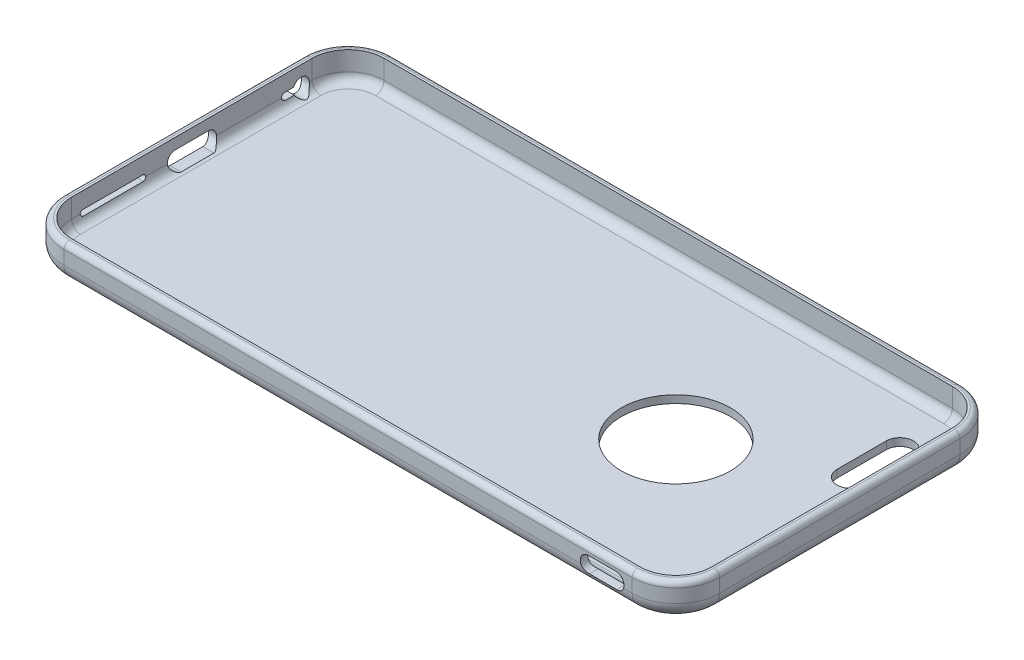
SolidWorks part; units mm, degrees
ref_plane "Front Plane" through (0, 0, 0) normal (0, 0, 1) x (1, 0, 0)
ref_plane "Top Plane" through (0, 0, 0) normal (0, 1, 0) x (1, 0, 0)
ref_plane "Right Plane" through (0, 0, 0) normal (1, 0, 0) x (0, 0, -1)
sketch "Sketch1" plane through (0, 0, 0) normal (0, 1, 0) x (1, 0, 0)
  line L1 (-76.2, -38.1) -> (76.2, -38.1)
  line L2 (-76.2, -38.1) -> (-76.2, 38.1)
  line L3 (-76.2, 38.1) -> (76.2, 38.1)
  line L4 (76.2, -38.1) -> (76.2, 38.1)
  dimension "D1" = 152.4
  dimension "D2" = 76.2
  dimension "D3" = 38.1
  dimension "D4" = 76.2
extrude "Boss-Extrude1" add sketch "Sketch1" along normal blind 8.255
fillet "Fillet1" radius 10.16 4 edges at (-76.2, 4.1275, -38.1) (76.2, 4.1275, -38.1) (76.2, 4.1275, 38.1) (-76.2, 4.1275, 38.1)
fillet "Fillet2" radius 3.81 8 edges at (73.2242, 0, -35.1242) (76.2, 0, 0) (73.2242, 0, 35.1242) (0, 0, 38.1) (-73.2242, 0, 35.1242) (-76.2, 0, 0) (-73.2242, 0, -35.1242) (0, 0, -38.1)
fillet "Fillet3" radius 1.27 8 edges at (73.2242, 8.255, -35.1242) (76.2, 8.255, 0) (73.2242, 8.255, 35.1242) (0, 8.255, 38.1) (-73.2242, 8.255, 35.1242) (-76.2, 8.255, 0) (-73.2242, 8.255, -35.1242) (0, 8.255, -38.1)
shell "Shell1" thickness 1.778 removed face at (0, 8.255, 0)
sketch "Sketch2" plane through (0, 0, 0) normal (0, -1, 0) x (1, 0, 0)
  circle A0 centre (38.1, 0) radius 12.7
  dimension "D1" = 25.4
  dimension "D2" = 38.1
extrude "Cut-Extrude1" cut sketch "Sketch2" against normal through all
sketch "Sketch3" plane through (0, 0, 0) normal (0, -1, 0) x (1, 0, 0)
  line L0 (66.04, -12.7) -> (66.04, -24.13) construction
  line L1 (69.215, -12.7) -> (69.215, -24.13)
  line L2 (62.865, -12.7) -> (62.865, -24.13)
  arc A0 (69.215, -12.7) -> (62.865, -12.7) centre (66.04, -12.7) ccw
  arc A1 (62.865, -24.13) -> (69.215, -24.13) centre (66.04, -24.13) ccw
  circle A2 centre (38.1, 0) radius 12.7 construction
  point P2 (66.04, -18.415)
  dimension "D1" = 12.7
  dimension "D2" = 11.43
  dimension "D3" = 3.175
  dimension "D4" = 27.94
extrude "Cut-Extrude2" cut sketch "Sketch3" against normal through all
sketch "Sketch4" plane through (0, 0, 0) normal (0, 0, 1) x (1, 0, 0)
  line L0 (62.23, 4.445) -> (55.88, 4.445) construction
  line L1 (62.23, 2.54) -> (55.88, 2.54)
  line L2 (62.23, 6.35) -> (55.88, 6.35)
  line L3 (74.93, 8.255) -> (66.04, 8.255) construction
  line L4 (76.2, 6.985) -> (76.2, 3.81) construction
  arc A0 (62.23, 2.54) -> (62.23, 6.35) centre (62.23, 4.445) ccw
  arc A1 (55.88, 6.35) -> (55.88, 2.54) centre (55.88, 4.445) ccw
  point P2 (59.055, 4.445)
  dimension "D1" = 1.905
  dimension "D2" = 6.35
  dimension "D3" = 3.81
  dimension "D4" = 13.97
extrude "Cut-Extrude3" cut sketch "Sketch4" along normal through all
sketch "Sketch5" plane through (0, 0, 0) normal (1, 0, 0) x (0, 0, -1)
  line L0 (3.81, 3.81) -> (-3.81, 3.81) construction
  line L1 (3.81, 1.905) -> (-3.81, 1.905)
  line L2 (3.81, 5.715) -> (-3.81, 5.715)
  line L3 (-27.94, 0) -> (27.94, 0) construction
  arc A0 (3.81, 1.905) -> (3.81, 5.715) centre (3.81, 3.81) ccw
  arc A1 (-3.81, 5.715) -> (-3.81, 1.905) centre (-3.81, 3.81) ccw
  point P2 (0, 3.81)
  dimension "D2" = 3.81
  dimension "D3" = 1.905
  dimension "D1" = 7.62
  dimension "D4" = 3.81
extrude "Cut-Extrude4" cut sketch "Sketch5" against normal through all
sketch "Sketch6" plane through (0, 0, 0) normal (1, 0, 0) x (0, 0, -1)
  line L0 (-11.345, 3.81) -> (-25.315, 3.81) construction
  line L1 (-11.345, 3.175) -> (-25.315, 3.175)
  line L2 (-11.345, 4.445) -> (-25.315, 4.445)
  line L3 (-27.94, 0) -> (27.94, 0) construction
  arc A0 (-11.345, 3.175) -> (-11.345, 4.445) centre (-11.345, 3.81) ccw
  arc A1 (-25.315, 4.445) -> (-25.315, 3.175) centre (-25.315, 3.81) ccw
  point P2 (-18.33, 3.81)
  dimension "D1" = 0.635
  dimension "D3" = 13.97
  dimension "D2" = 3.175
extrude "Cut-Extrude5" cut sketch "Sketch6" against normal through all
sketch "Sketch7" plane through (0, 0, 0) normal (1, 0, 0) x (0, 0, -1)
  line L0 (25.4, 3.81) -> (21.59, 3.81) construction
  line L1 (25.4, 3.048) -> (21.59, 3.048)
  line L2 (25.4, 4.572) -> (21.59, 4.572)
  line L3 (-27.94, 0) -> (27.94, 0) construction
  line L4 (38.1, 3.81) -> (38.1, 6.985) construction
  arc A0 (25.4, 3.048) -> (25.4, 4.572) centre (25.4, 3.81) ccw
  arc A1 (21.59, 4.572) -> (21.59, 3.048) centre (21.59, 3.81) ccw
  point P2 (23.495, 3.81)
  dimension "D1" = 0.762
  dimension "D2" = 3.81
  dimension "D3" = 3.81
  dimension "D4" = 12.7
extrude "Cut-Extrude6" cut sketch "Sketch7" against normal through all
sketch "Sketch8" plane through (0, 0, 0) normal (1, 0, 0) x (0, 0, -1)
  circle A0 centre (25.4, 3.81) radius 1.905
  arc A1 (26.162, 3.81) -> (25.4, 4.572) centre (25.4, 3.81) ccw construction
  dimension "D1" = 3.81
extrude "Cut-Extrude7" cut sketch "Sketch8" against normal through all
